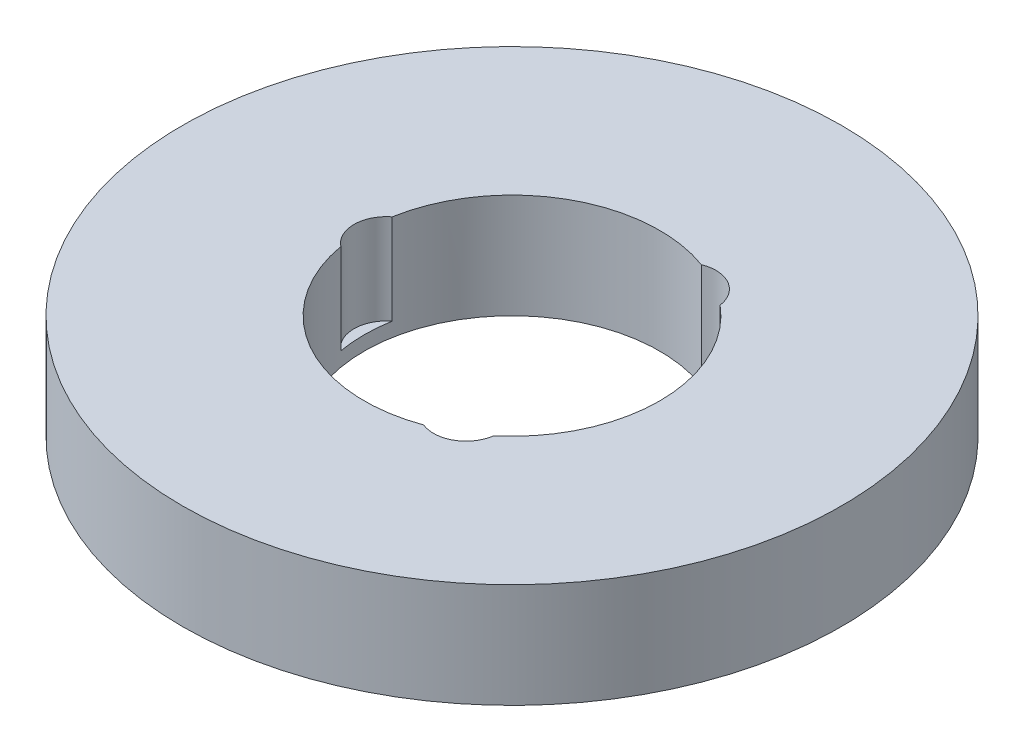
SolidWorks part; units mm, degrees
ref_plane "Front Plane" through (0, 0, 0) normal (0, 0, 1) x (1, 0, 0)
ref_plane "Top Plane" through (0, 0, 0) normal (0, 1, 0) x (1, 0, 0)
ref_plane "Right Plane" through (0, 0, 0) normal (1, 0, 0) x (0, 0, -1)
sketch "Sketch1" plane through (0, 0, 0) normal (0, 1, 0) x (1, 0, 0)
  circle A0 centre (0, 0) radius 72.5
  dimension "FLANGE_OD" = 145
extrude "Boss-Extrude1" add sketch "Sketch1" along normal blind 23
sketch "Sketch2" plane through (0, 0, 0) normal (0, 1, 0) x (1, 0, 0)
  circle A0 centre (0, 0) radius 32.5
  dimension "BORE_D" = 65
extrude "Cut-Extrude1" cut sketch "Sketch2" along normal through all
sketch "Sketch3" plane through (0, 23, 0) normal (0, 1, 0) x (1, 0, 0)
  circle A0 centre (0, 0) radius 27.6051 construction
  circle A1 centre (-27.6051, 0) radius 7.1602
  dimension "BOLT_D" = 14.3203
  dimension "BOLT_PCD" = 55.2103
extrude "Cut-Extrude2" cut sketch "Sketch3" against normal blind 19.8797
pattern_circular "CirPattern1" count 3 over 360 about axis through (0, 0, 0) along (0, 1, 0) of "Cut-Extrude2"
